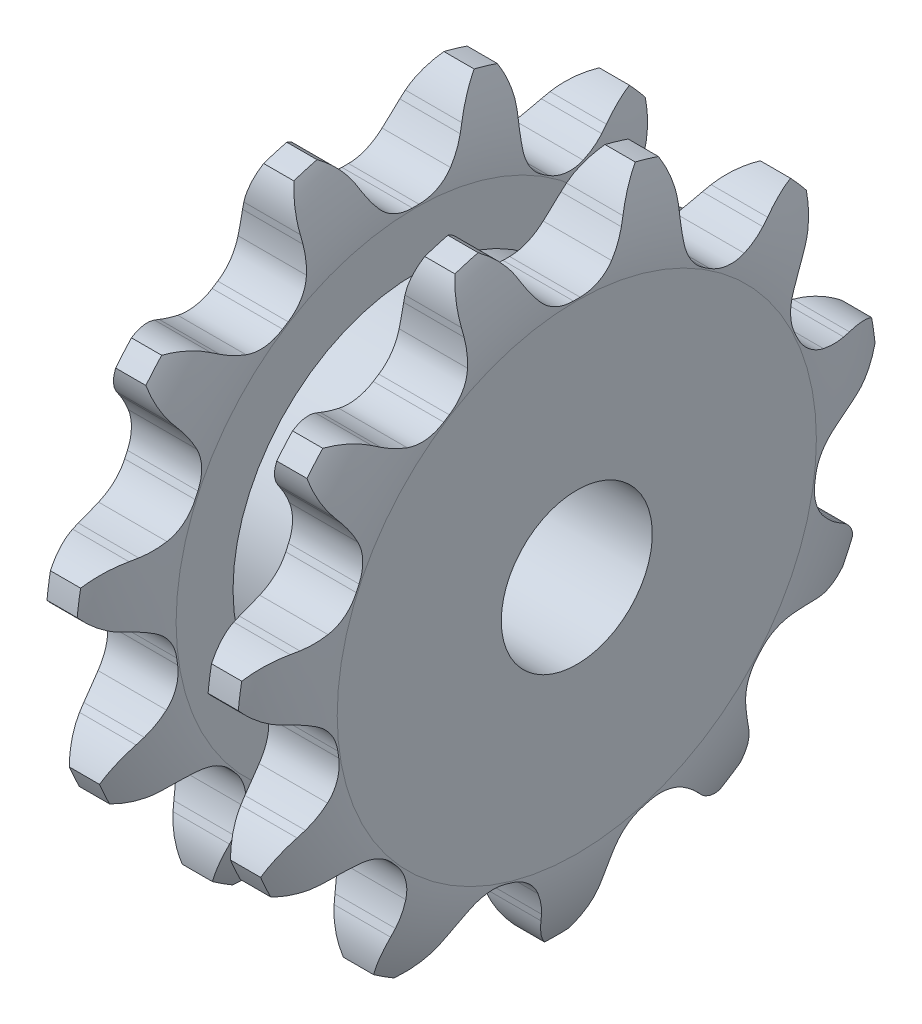
SolidWorks part; units mm, degrees
ref_plane "Plane1" through (0, 0, 0) normal (0, 0, 1) x (1, 0, 0)
ref_plane "Plane2" through (0, 0, 0) normal (0, 1, 0) x (1, 0, 0)
ref_plane "Plane3" through (0, 0, 0) normal (1, 0, 0) x (0, 0, -1)
sketch "Clipboard" plane through (0, 0, 0) normal (0, 1, 0) x (1, 0, 0)
  line L0 (0, 0) -> (6.2333, -1.2116)
  line L1 (-15, 0) -> (100, 0) construction
  line L2 (0, 0) -> (-0.5301, 0.5991)
  line L3 (0, 0) -> (-2.9891, 1.1425)
  line L4 (0, 0) -> (3.043, 0.5915)
  line L5 (0, 0) -> (-89.0105, -33.1983)
  line L6 (0, 0) -> (-7.6265, -5.1456)
  line L7 (-0.5301, 0.5991) -> (92.0355, 21.9696)
  line L8 (-76.2, 38.1) -> (-75.2, 38.1)
  line L9 (-73.2358, 39.4872) -> (-73.0836, 39.4947)
  line L10 (-73.0533, 76.1892) -> (-66.6533, 76.1892)
  circle A0 centre (0, 0) radius 1.651
  circle A1 centre (0, 0) radius 4
  circle A2 centre (0, 0) radius 4
  dimension "Num_teeth" = 11
  dimension "Thickness" = 9.2
sketch "BasProSke" plane through (0, 0, 0) normal (0, 1, 0) x (1, 0, 0)
  line L0 (-10, 0) -> (60, 0) construction
  line L1 (0, 0) -> (0, 9.5181)
  line L2 (0, 0) -> (9.2, 0)
  line L3 (9.2, 0) -> (9.2, 9.5181)
  line L4 (8.4, 12.7181) -> (0.8, 12.7181)
  arc A0 (0, 9.5181) -> (0.8, 12.7181) centre (6.8, 9.5181) cw
  arc A1 (9.2, 9.5181) -> (8.4, 12.7181) centre (2.4, 9.5181) ccw
  dimension "D1" = 6.8
  dimension "Thickness" = 9.2
  dimension "Diameter" = 25.4361
  dimension "H1" = 3.2
  dimension "G1" = 0.8
revolve "Base-Revolve" add sketch "BasProSke" angle 360 about L0
sketch "GrvSke" plane through (0, 0, 0) normal (0, 1, 0) x (1, 0, 0)
  line L0 (2.8, 9.5181) -> (2.8, 7.2571)
  line L1 (2.8, 7.2571) -> (6.4, 7.2571)
  line L2 (6.4, 7.2571) -> (6.4, 9.5181)
  line L3 (2, 12.7181) -> (7.2, 12.7181)
  line L4 (4.6, 0) -> (4.6, 52.07) construction
  line L5 (-10, 0) -> (60, 0) construction
  line L6 (0, 0) -> (35.56, 0) construction
  arc A0 (6.4, 9.5181) -> (7.2, 12.7181) centre (13.2, 9.5181) cw
  arc A1 (2.8, 9.5181) -> (2, 12.7181) centre (-4, 9.5181) ccw
  dimension "Diameter" = 25.4361
  dimension "H1" = 3.2
  dimension "G1" = 0.8
revolve "Groove" cut sketch "GrvSke" angle 360 about L6
pattern_linear "Grooves" [suppressed]
sketch "TooCutSke" plane through (0, 0, 0) normal (1, 0, 0) x (0, 0, -1)
  line L0 (1.9692, 10.9762) -> (2.1109, 11.2478)
  line L1 (0, 0) -> (0, 107) construction
  line L2 (0.2483, 11.2688) -> (-2.0258, 11.2688) construction
  line L4 (0.1322, 12.3974) -> (0.1322, 8.6148) construction
  line L5 (0.1322, 9.5714) -> (-0.1322, 9.5714)
  line L6 (-1.9692, 10.9762) -> (-2.1109, 11.2478)
  arc A0 (1.4237, 10.1675) -> (1.9692, 10.9762) centre (-1.8779, 12.9828) ccw
  arc A1 (1.4237, 10.1675) -> (0.1322, 9.5714) centre (0.1322, 11.2688) cw
  arc A2 (2.1109, 11.2478) -> (4.5677, 12.7373) centre (4.5677, 9.9664) cw
  arc A3 (-0.1322, 9.5714) -> (-1.4237, 10.1675) centre (-0.1322, 11.2688) cw
  arc A4 (-1.4237, 10.1675) -> (-1.9692, 10.9762) centre (1.8779, 12.9828) cw
  arc A5 (-2.1109, 11.2478) -> (-4.5677, 12.7373) centre (-4.5677, 9.9664) ccw
  arc A6 (4.5677, 12.7373) -> (-4.5677, 12.7373) centre (0, 0) ccw
  dimension "Pitch_radius" = 11.2696
  dimension "V" = 1.3024
  dimension "D1" = 1.8779
extrude "ToothCut" cut sketch "TooCutSke" along normal through all
pattern_circular "TeethCuts" count 11 every 32.727 about axis through (-10, 0, 0) along (1, 0, 0) of "ToothCut"
sketch "HubNeaOneSke" plane through (0, 0, 0) normal (-1, 0, 0) x (0, 0, 1)
  circle A0 centre (0, 0) radius 4
  dimension "Diameter" = 8
extrude "HubNearOne" [suppressed] add sketch "HubNeaOneSke" along normal blind 85.8005
sketch "HubNeaBotSke" plane through (0, 0, 0) normal (-1, 0, 0) x (0, 0, 1)
  circle A0 centre (0, 0) radius 4
  dimension "Diameter" = 8
extrude "HubNearBoth" [suppressed] add sketch "HubNeaBotSke" along normal blind 42.9002
ref_plane "FarPln" through (9.2, 0, 0) normal (1, 0, 0) x (0, 0, -1)
sketch "HubFarSke" plane through (9.2, 0, 0) normal (1, 0, 0) x (0, 0, -1)
  circle A0 centre (0, 0) radius 4
  dimension "Diameter" = 8
extrude "HubFar" [suppressed] add sketch "HubFarSke" along normal blind 42.9002
sketch "BorSke" plane through (0, 0, 0) normal (1, 0, 0) x (0, 0, -1)
  circle A0 centre (0, 0) radius 3
  dimension "Diameter" = 6
extrude "Bore" cut sketch "BorSke" along normal mid plane 190.001
sketch "KeySke" plane through (0, 0, 0) normal (1, 0, 0) x (0, 0, -1)
  line L0 (-1, 0) -> (-1, 4)
  line L1 (-1, 4) -> (1, 4)
  line L2 (1, 4) -> (1, 0)
  line L3 (0, 0) -> (0, 34) construction
  line L4 (-1, 0) -> (1, 0)
  dimension "Offset" = 4
  dimension "Width" = 2
extrude "Keyway" [suppressed] cut sketch "KeySke" along normal mid plane 190.001
pattern_circular "Keyway2" [suppressed] count 2 every 90 about axis through (-10, 0, 0) along (1, 0, 0)
equation "' \"Pitch@Clipboard\" = 6.35"
equation "' \"Num_strands@Clipboard\" = 2"
equation "' \"Num_teeth@Clipboard\" = 11"
equation "' \"Hub_dia@Clipboard\" = 8"
equation "' \"Overall_len@Clipboard\" = 95"
equation "' \"Diameter@BorSke\" = 6"
equation "' \"T_dim@Clipboard\" = 1"
equation "' \"Width@KeySke\" = 2"
equation "' \"Dr@Clipboard\" = 3.302"
equation "' \"Face_width@Clipboard\" = 2.8"
equation "' \"Chamfer_dep@Clipboard\" = 3.2"
equation "' \"Chamfer_wid@Clipboard\" = 0.8"
equation "' \"Transv_pitch@Clipboard\" = 6.4"
equation "' \"Show_teeth@Clipboard\" = 11"
equation "\"Num_teeth@Clipboard\" = int( \"Num_teeth@Clipboard\" )"
equation "\"Num_teeth@Clipboard\" = ((sgn( \"Num_teeth@Clipboard\" - 5.0)+1)*( \"Num_teeth@Clipboard\" - 5.0))/2 +5.0"
equation "\"Num_teeth@Clipboard\" = ((sgn( \"Num_teeth@Clipboard\" - 200.0)-1)*( \"Num_teeth@Clipboard\" - 200.0))/-2 +200.0"
equation "\"MHD@Clipboard\" = \"Pitch@Clipboard\" * (1.0 / tan(3.14159265 / \"Num_teeth@Clipboard\" ) - 1.0) - 0.762"
equation "\"Thickness@Clipboard\"  = \"Face_width@Clipboard\" + (\"Num_strands@Clipboard\" - 1) * \"Transv_pitch@Clipboard\""
equation "\"OAL@Clipboard\" = \"Thickness@Clipboard\""
equation "\"MHD@Clipboard\" = ((sgn( \"MHD@Clipboard\" - \"Hub_dia@Clipboard\" )-1)*( \"MHD@Clipboard\" - \"Hub_dia@Clipboard\" ))/-2+ \"Hub_dia@Clipboard\""
equation "\"OAL@Clipboard\" = ((sgn( \"OAL@Clipboard\" - \"Overall_len@Clipboard\" )+1)*( \"OAL@Clipboard\" - \"Overall_len@Clipboard\" ))/2 + \"Overall_len@Clipboard\" + 0.0005"
equation "\"Num_teeth@TeethCuts\" = int( \"Show_teeth@Clipboard\" ) + 1"
equation "\"Num_teeth@TeethCuts\" = ((sgn( \"Num_teeth@TeethCuts\" - \"Num_teeth@Clipboard\" )-1)*( \"Num_teeth@TeethCuts\" - \"Num_teeth@Clipboard\" ))/-2+ \"Num_teeth@Clipboard\""
equation "\"Num_teeth@TeethCuts\" = ((sgn( \"Num_teeth@TeethCuts\" - 2.0)+1)*( \"Num_teeth@TeethCuts\" - 2.0))/2 +2.0"
equation "\"Angle@TeethCuts\" = 360.0 / \"Num_teeth@Clipboard\""
equation "\"Pitch_radius@TooCutSke\" = ( \"Pitch@Clipboard\" / 2.0) / sin(3.14159265 / \"Num_teeth@Clipboard\" )  'ma"
equation "\"Half_U@TooCutSke\" = 0.5 * (0.07 * (\"Pitch@Clipboard\" - \"Dr@Clipboard\") + 0.051)"
equation "\"R@TooCutSke\"  = \"Dr@Clipboard\" * 0.5025 + 0.0381"
equation "\"A@TooCutSke\" = 35.0 + (60.0 / \"Num_teeth@Clipboard\")"
equation "\"E@TooCutSke\"  = \"Dr@Clipboard\" * 1.3025 + 0.0381"
equation "\"B@TooCutSke\"  = 18.0 - (56.0 / \"Num_teeth@Clipboard\" )"
equation "\"W@TooCutSke\" = 1.4 * \"Dr@Clipboard\" * cos(3.14159265 / \"Num_teeth@Clipboard\" ) + \"Half_U@TooCutSke\""
equation "\"V@TooCutSke\" = 1.4 * \"Dr@Clipboard\" * sin(3.14159265 / \"Num_teeth@Clipboard\" )"
equation "\"Diameter@BasProSke\" = 2.0 * ( (0.3 * \"Pitch@Clipboard\" ) +  \"Pitch@Clipboard\" / 2.0 / tan(3.14159265 / \"Num_teeth@Clipboard\" ))"
equation "\"Thickness@BasProSke\"  = \"Thickness@Clipboard\""
equation "\"G1@BasProSke\" =  \"Chamfer_wid@Clipboard\""
equation "\"G2@BasProSke\" =  \"Chamfer_wid@Clipboard\""
equation "\"H1@BasProSke\" =  \"Chamfer_dep@Clipboard\""
equation "\"H2@BasProSke\" =  \"Chamfer_dep@Clipboard\""
equation "\"Diameter@GrvSke\" = \"Diameter@BasProSke\""
equation "\"G1@GrvSke\" = \"Chamfer_wid@Clipboard\""
equation "\"H1@GrvSke\" = \"Chamfer_dep@Clipboard\""
equation "\"Grv_diam@GrvSke\" =  \"Pitch@Clipboard\" * (1.0 / tan(3.14159265 / \"Num_teeth@Clipboard\" ) - 1.0) - 0.762"
equation "\"Grv_width@GrvSke\" =  \"Transv_pitch@Clipboard\" - \"Face_width@Clipboard\""
equation "\"Offset@GrvSke\" = \"Grv_width@GrvSke\" / 2.0 + \"Face_width@Clipboard\""
equation "\"Offset@Grooves\" = \"Transv_pitch@Clipboard\""
equation "\"Num_grvs@Grooves\" = \"Num_strands@Clipboard\""
equation "\"Num_grvs@Grooves\" = \"Num_grvs@Grooves\" - 1 * sgn( \"Num_grvs@Grooves\" -1)"
equation "\"Diameter@HubNeaOneSke\" = \"MHD@Clipboard\""
equation "\"Length@HubNearOne\" = \"OAL@Clipboard\" - \"Thickness@BasProSke\""
equation "\"Diameter@HubNeaBotSke\" = \"MHD@Clipboard\""
equation "\"Length@HubNearBoth\" = ( \"OAL@Clipboard\" - \"Thickness@BasProSke\" ) / 2.0"
equation "\"Thickness@FarPln\" = \"Thickness@BasProSke\""
equation "\"Diameter@HubFarSke\" = \"MHD@Clipboard\""
equation "\"Length@HubFar\" = ( \"OAL@Clipboard\" - \"Thickness@BasProSke\" ) / 2.0"
equation "\"D1@Bore\" = \"OAL@Clipboard\" * 2.0"
equation "\"D1@Keyway\" = \"OAL@Clipboard\" * 2.0"
equation "\"Offset@KeySke\" = \"T_dim@Clipboard\" + \"Diameter@BorSke\" / 2.0"
